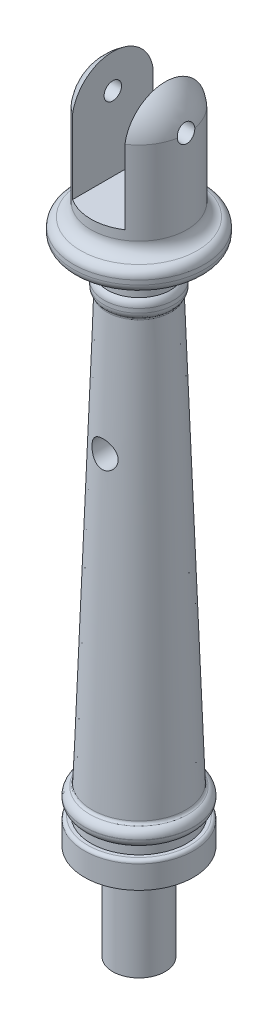
SolidWorks part; units mm, degrees
ref_plane "Front Plane" through (0, 0, 0) normal (0, 0, 1) x (1, 0, 0)
ref_plane "Top Plane" through (0, 0, 0) normal (0, 1, 0) x (1, 0, 0)
ref_plane "Right Plane" through (0, 0, 0) normal (1, 0, 0) x (0, 0, -1)
sketch "Sketch2" plane through (0, 0, 0) normal (0, 0, 1) x (1, 0, 0)
  line L0 (0, 0) -> (11, 0)
  line L1 (11, 0) -> (7, 114)
  line L2 (7, 114) -> (0, 114)
  line L3 (0, 114) -> (0, 0)
  dimension "D1" = 114
  dimension "D2" = 7
  dimension "D3" = 11
revolve "Revolve2" add sketch "Sketch2" angle 360 about L3
sketch "Sketch3" plane through (0, 0, 0) normal (0, -1, 0) x (1, 0, 0)
  circle A0 centre (0, 0) radius 12.5
  dimension "D1" = 25
extrude "Boss-Extrude1" add sketch "Sketch3" along normal blind 6
sketch "Sketch5" plane through (0, -6, 0) normal (0, -1, 0) x (1, 0, 0)
  circle A1 centre (0, 0) radius 12.5
  circle A2 centre (0, 0) radius 12.5
  dimension "D1" = 0
sketch "Sketch6" plane through (0, -6, 0) normal (0, -1, 0) x (1, 0, 0)
  circle A1 centre (0, 0) radius 12.5
  circle A2 centre (0, 0) radius 12.5
  dimension "D1" = 0
extrude "Boss-Extrude4" add sketch "Sketch6" along normal blind 4 from offset 12 offset against normal yes
fillet "Fillet1" radius 2 2 edges at (0, 6, -12.5) (0, 2, -12.5)
fillet "Fillet2" radius 0.75 2 edges at (0, 6, -10.7895) (0, 0, -12.5)
sketch "Sketch7" plane through (0, -6, 0) normal (0, -1, 0) x (1, 0, 0)
  circle A0 centre (0, 0) radius 6
  dimension "D1" = 12
extrude "Boss-Extrude5" add sketch "Sketch7" along normal blind 22 contours A0
sketch "Sketch8" plane through (0, -28, 0) normal (0, -1, 0) x (1, 0, 0)
  line L0 (-5.1417, 3.0923) -> (-4.8485, -3.5344)
  circle A1 centre (0, 0) radius 6
  arc A2 (-5.1417, 3.0923) -> (-4.8485, -3.5344) centre (0, 0) ccw
  dimension "D2" = 5
  dimension "D1" = 0
extrude "Cut-Extrude2" cut sketch "Sketch8" against normal blind 15
sketch "Sketch9" plane through (0, 114, 0) normal (0, 1, 0) x (1, 0, 0)
  circle A0 centre (0, 0) radius 8
  dimension "D1" = 16
extrude "Boss-Extrude6" add sketch "Sketch9" along normal mid plane 4 from offset 8 offset against normal yes
fillet "Fillet3" radius 2 2 edges at (0, 104, 8) (0, 108, 8)
fillet "Fillet4" radius 0.75 1 edges at (0, 104, 7.3509)
sketch "Sketch10" plane through (0, 114, 0) normal (0, 1, 0) x (1, 0, 0)
  circle A0 centre (0, 0) radius 15
  dimension "D1" = 30
extrude "Boss-Extrude7" add sketch "Sketch10" along normal blind 5 contours A0
sketch "Sketch11" plane through (0, 119, 0) normal (0, 1, 0) x (1, 0, 0)
  circle A0 centre (0, 0) radius 11
  dimension "D1" = 22
extrude "Boss-Extrude8" add sketch "Sketch11" along normal blind 22
fillet "Fillet5" radius 2 2 edges at (0, 114, 15) (0, 119, 15)
fillet "Fillet6" radius 3 1 edges at (0, 119, 11)
fillet "Fillet7" radius 2 1 edges at (0, 114, 7)
sketch "Sketch13" plane through (0, 0, 0) normal (0, 0, 1) x (1, 0, 0)
  line L0 (11, 141) -> (0, 141)
  line L1 (11, 141) -> (-11, 141) construction
  line L2 (0, 141) -> (0, 150.5)
  arc A0 (0, 150.5) -> (11, 141) centre (0.1027, 139.5005) cw
  dimension "D2" = 11
  dimension "D1" = 9.5
revolve "Revolve4" add sketch "Sketch13" angle 360 about L2
sketch "Sketch14" plane through (0, 0, 0) normal (0, 0, 1) x (1, 0, 0)
  line L0 (0, 121.899) -> (0, 153.4079) construction
  line L1 (11, 121.899) -> (-11, 121.899) construction
  line L2 (11, 141) -> (-11, 141) construction
  line L3 (-6, 151.4181) -> (6, 151.4181)
  line L4 (-6, 151.4181) -> (-6, 124)
  line L5 (-6, 124) -> (6, 124)
  line L6 (6, 151.4181) -> (6, 124)
  line L7 (-6, 151.4181) -> (6, 124) construction
  line L8 (-6, 124) -> (6, 151.4181) construction
  point P5 (0, 137.709)
  point P10 (0, 0)
  dimension "D1" = 27.4181
  dimension "D2" = 17
  dimension "D3" = 12
extrude "Cut-Extrude3" cut sketch "Sketch14" against normal mid plane 22
sketch "Sketch15" plane through (0, 0, 0) normal (0, 0, 1) x (1, 0, 0)
  circle A0 centre (0, 76) radius 3
  point P2 (0, 0)
  dimension "D2" = 6
  dimension "D1" = 82
extrude "Cut-Extrude4" cut sketch "Sketch15" against normal mid plane 22 contours A0
sketch "Sketch16" plane through (0, 0, 0) normal (1, 0, 0) x (0, 0, -1)
  line L0 (-9.2195, 141) -> (9.2195, 141) construction
  line L1 (-13, 114) -> (13, 114) construction
  circle A0 centre (0, 141) radius 2
  dimension "D1" = 4
  dimension "D2" = 27
extrude "Cut-Extrude5" cut sketch "Sketch16" against normal mid plane 22
